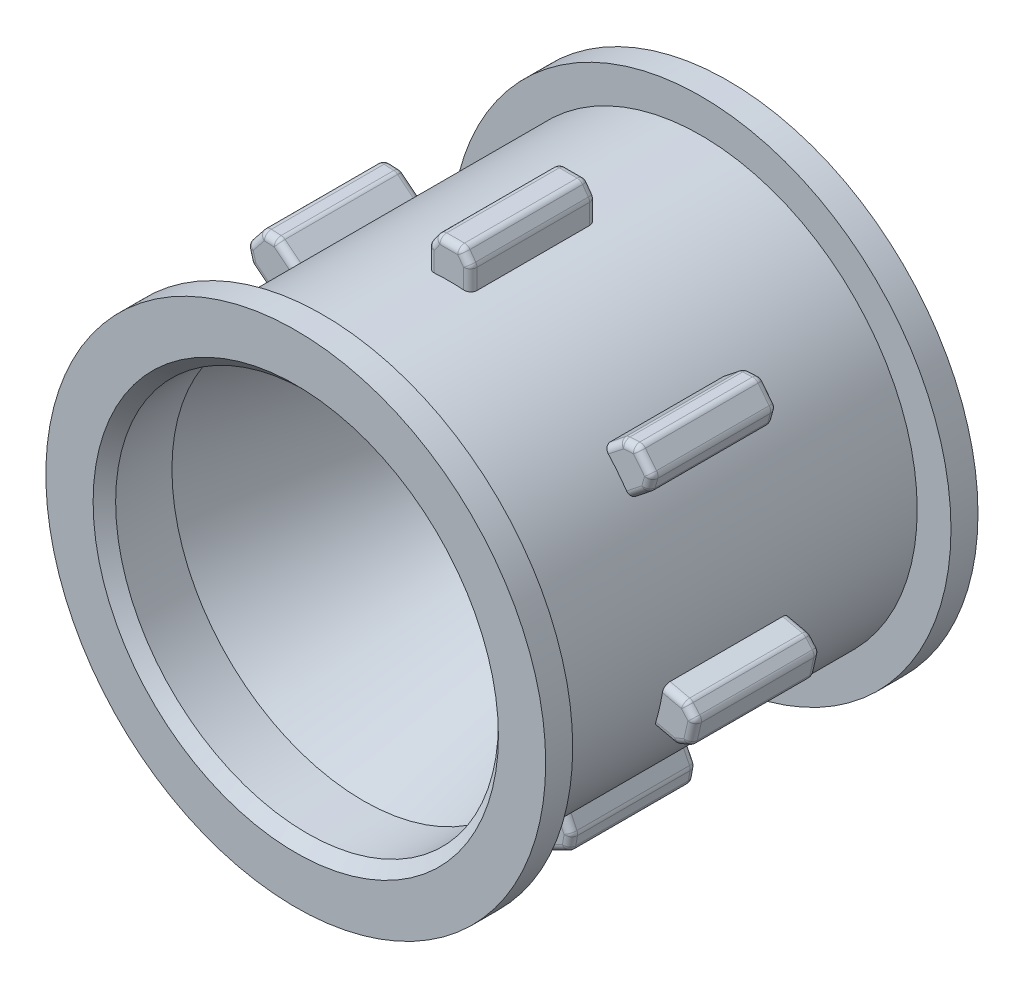
SolidWorks part; units mm, degrees
ref_plane "Ebene vorne" through (0, 0, 0) normal (0, 0, 1) x (1, 0, 0)
ref_plane "Ebene oben" through (0, 0, 0) normal (0, 1, 0) x (1, 0, 0)
ref_plane "Ebene rechts" through (0, 0, 0) normal (1, 0, 0) x (0, 0, -1)
sketch "Skizze1" plane through (0, 0, 0) normal (0, 0, 1) x (1, 0, 0)
  circle A0 centre (0, 0) radius 9.6
  dimension "D1" = 19.2
extrude "Laufrad" add sketch "Skizze1" along normal blind 8.4 and the other way blind 8.4
sketch "Skizze2" plane through (0, 0, 8.4) normal (0, 0, 1) x (1, 0, 0)
  circle A0 centre (0, 0) radius 11.1
  circle A1 centre (0, 0) radius 9.6 construction
  dimension "D1" = 1.5
extrude "Kettenführung" add sketch "Skizze2" along normal blind 1.2
mirror "Spiegeln Kettenführung" about plane through (0, 0, 0) normal (0, 0, 1) of "Kettenführung"
sketch "Skizze4" plane through (0, 0, -9.6) normal (0, 0, -1) x (-1, 0, 0)
  circle A0 centre (0, 0) radius 1.65
  dimension "D1" = 3.3
extrude "SchraubenBohrung M3" cut sketch "Skizze4" against normal through all
sketch "Skizze3" plane through (0, 0, -9.6) normal (0, 0, -1) x (-1, 0, 0)
  circle A0 centre (0, 0) radius 4.1
  dimension "D1" = 8.2
extrude "Kugellagersitz" cut sketch "Skizze3" against normal blind 4
sketch "Skizze5" plane through (0, 0, 0) normal (1, 0, 0) x (0, 0, -1)
  line L0 (-9.6, 0) -> (-9.6, 8.5)
  line L1 (-9.6, 8.5) -> (-6.6, 8.5)
  line L2 (-6.6, 8.5) -> (2.6, 6)
  line L3 (2.6, 6) -> (2.6, 0)
  line L4 (9.6, -4.1) -> (9.6, 4.1) construction
  line L5 (-9.6, 0) -> (5.6, 0) construction
  line L6 (-9.6, 0) -> (2.6, 0)
  line L7 (-9.6, 11.1) -> (-9.6, -11.1) construction
  dimension "D1" = 7
  dimension "D2" = 3
  dimension "D3" = 8.5
  dimension "D4" = 6
revolve "Schnitt-Rotation3" cut sketch "Skizze5" angle 360 about axis through (0, 0, -8.4) along (0, 0, 1)
chamfer "Fase1" distance 0.5 angle 45 5 edges at (-1.65, 0, -2.6) (-1.65, 0, -5.6) (-4.1, 0, -9.6) (-8.5, 0, 9.6) (-6, 0, -2.6) first distance on face at (-6, 0, -2.6) first distance on face at (-1.65, 0, -2.6) first distance on face at (-4.1, 0, -9.6) first distance on face at (-8.5, 0, 9.6)
sketch "Skizze6" plane through (0, 0, 0) normal (0, 0, 1) x (1, 0, 0)
  line L0 (0, 0) -> (0, 10.3) construction
  line L1 (0, 10.3) -> (0, 11.1) construction
  line L2 (0.55, 11.1) -> (-0.55, 11.1)
  line L3 (-0.55, 11.1) -> (-0.95, 10.5424)
  line L4 (-0.95, 10.5424) -> (-0.95, 9.5529)
  line L5 (0.95, 10.5424) -> (0.95, 9.5529)
  line L6 (0.55, 11.1) -> (0.95, 10.5424)
  line L7 (-0.95, 9.5529) -> (0.95, 9.5529)
  circle A1 centre (0, 0) radius 9.6 construction
  dimension "D1" = 0.8
  dimension "D2" = 10.3
  dimension "D3" = 1.9
  dimension "D4" = 1.1
extrude "Zahn" add sketch "Skizze6" along normal blind 2.8 and the other way blind 2.8
fillet "Verrundung1" radius 0.3 14 edges at (0.95, 10.5424, 0) (-0.95, 10.5424, 0) (-0.95, 10.0476, -2.8) (-0.75, 10.8212, -2.8) (0, 11.1, -2.8) (0.75, 10.8212, -2.8) (0.95, 10.0476, -2.8) (-0.55, 11.1, 0) (0.55, 11.1, 0) (-0.95, 10.0476, 2.8) (-0.75, 10.8212, 2.8) (0, 11.1, 2.8) (0.75, 10.8212, 2.8) (0.95, 10.0476, 2.8)
pattern_circular "Kreismuster1" count 7 over 360 about axis through (0, 0, -8.4) along (0, 0, 1) of "Zahn", "Verrundung1"
sketch "Skizze8" plane through (0, 0, -9.6) normal (0, 0, -1) x (-1, 0, 0)
  line L0 (0, 11.1) -> (0, -11.1) construction
  line L1 (0, -11.1) -> (0, 11.1) construction
  line L2 (11.1, 0) -> (-11.1, 0) construction
  line L3 (2, 8.5) -> (2, -8.5)
  line L4 (2, -8.5) -> (-2, -8.5)
  line L5 (-2, -8.5) -> (-2, 8.5)
  line L6 (-2, 0) -> (2, 0)
  line L7 (2, 8.5) -> (-2, 8.5)
  circle A0 centre (0, 0) radius 11.1 construction
  point P12 (0, 0)
  circle M6 centre (0, 0) radius 4.6
  dimension "D1" = 8.5
  dimension "D2" = 2
  dimension "D3" = 2
extrude "Auschnitt Antrieb Wage" cut sketch "Skizze8" against normal blind 2 contours L5 L6 L3 M6 | L3 L7 L5 M6 | L6 L5 L3 M6 | L5 L4 L3 M6 region at (0, 6.4731, -9.6) region at (0, 2.2274, -9.6) region at (0, -2.2274, -9.6) region at (0, -6.4731, -9.6)
sketch "Skizze10" plane through (0, 0, -9.6) normal (0, 0, -1) x (-1, 0, 0)
  line L0 (0, 11.1) -> (0, -11.1) construction
  line L1 (0, 10.56) -> (0, -10.56) construction
  line L2 (-8.5, 3.5) -> (8.5, 3.5)
  line L3 (8.5, 3.5) -> (8.5, -3.5)
  line L4 (8.5, -3.5) -> (-8.5, -3.5)
  line L5 (0, -3.5) -> (0, 3.5)
  line L6 (10.56, 0) -> (-10.56, 0) construction
  line L7 (-8.5, 3.5) -> (-8.5, -3.5)
  circle A0 centre (0, 0) radius 11.1 construction
  arc M7 (-2, -4.1425) -> (-2, 4.1425) centre (0, 0) cw
  arc M11 (2, 4.1425) -> (2, -4.1425) centre (0, 0) cw
  dimension "D1" = 8.5
  dimension "D2" = 3.5
  dimension "D3" = 3.5
extrude "Schnitt-Linear austragen2" cut sketch "Skizze10" against normal blind 2 contours L4 L3 L2 M11 | L2 L7 L4 M7 | L4 L5 L2 M7 | L5 L4 L2 M11 region at (6.2785, 0, -9.6) region at (2.0794, 0, -9.6) region at (-2.0794, 0, -9.6) region at (-6.2785, 0, -9.6)
